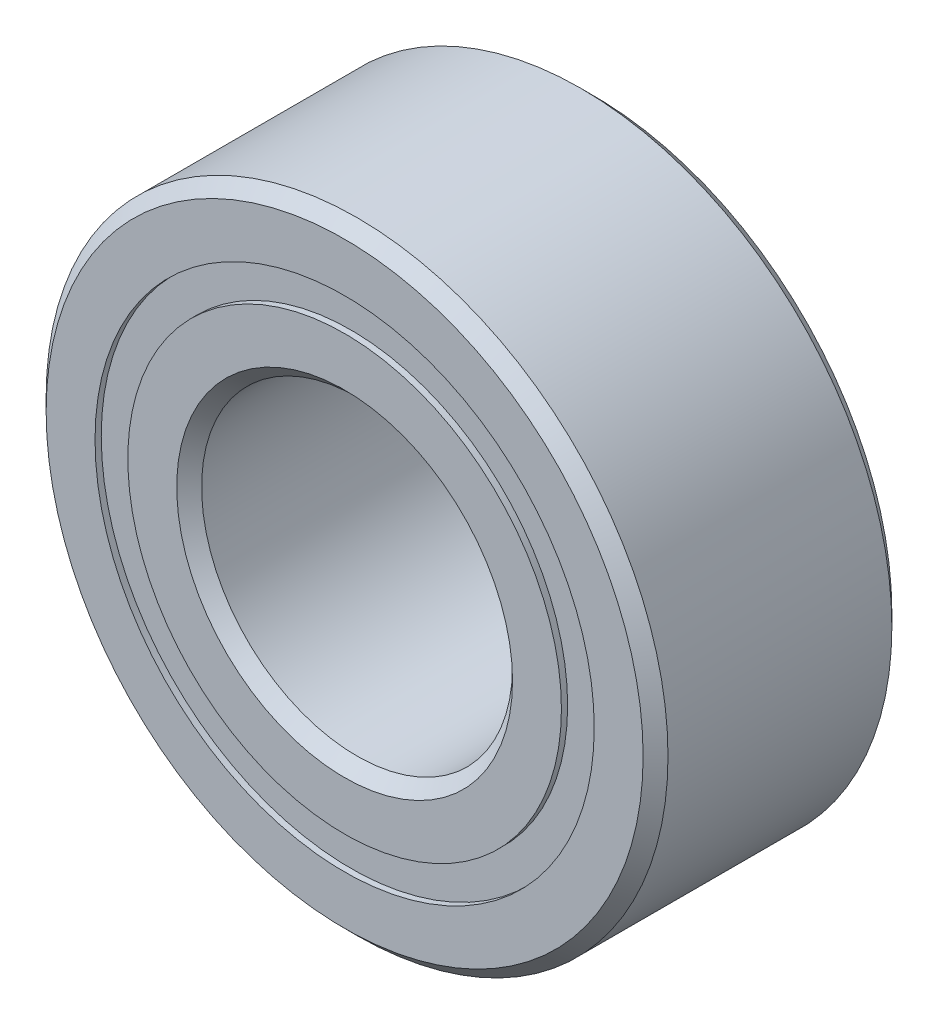
SolidWorks part; units mm, degrees
material "AISI 304"
ref_plane "Front Plane" through (0, 0, 0) normal (0, 0, 1) x (1, 0, 0)
ref_plane "Top Plane" through (0, 0, 0) normal (0, 1, 0) x (1, 0, 0)
ref_plane "Right Plane" through (0, 0, 0) normal (1, 0, 0) x (0, 0, -1)
sketch "Sketch1" plane through (0, 0, 0) normal (1, 0, 0) x (0, 0, -1)
  line L0 (-2, 0) -> (2, 0) construction
  line L1 (0, 5) -> (0, -5) construction
  line L2 (1.8, 5) -> (-1.8, 5)
  line L3 (-1.8, 5) -> (-2, 4.8)
  line L4 (-2, 4.8) -> (-2, 4.0137)
  line L5 (-2, 4.0137) -> (-0.8889, 4.0137)
  line L6 (2, 4.0137) -> (0.8889, 4.0137)
  line L7 (2, 4.8) -> (2, 4.0137)
  line L8 (1.8, 5) -> (2, 4.8)
  line L9 (0, 5) -> (0, 3.75) construction
  line L10 (0, 3.75) -> (0, 2.5) construction
  arc A0 (-0.8889, 4.0137) -> (0.8889, 4.0137) centre (0, 3.75) cw
  point P14 (0, 2.5)
  dimension "Width" = 4
  dimension "OD" = 10
  dimension "D1" = 45
  dimension "D2" = 0.2
  dimension "Shaft Dia" = 5
  dimension "D3" = 1.7778
  dimension "D4" = 0.2637
revolve "Revolve1" add sketch "Sketch1" angle 360 about L0
sketch "Sketch3" plane through (0, 0, 0) normal (1, 0, 0) x (0, 0, -1)
  line L0 (-2, 3.4863) -> (-0.8889, 3.4863)
  line L1 (0, 5) -> (0, -5) construction
  line L2 (-2, 4.8) -> (-2, 4.0137) construction
  line L3 (-2, 3.4863) -> (-2, 2.7)
  line L4 (-1.8, 5) -> (-2, 4.8) construction
  line L5 (-2, 2.7) -> (-1.8, 2.5)
  line L6 (-1.8, 2.5) -> (1.8, 2.5)
  line L7 (1.8, 5) -> (1.8, -5) construction
  line L8 (1.8, 2.5) -> (2, 2.7)
  line L9 (2, -4.8) -> (2, 4.8) construction
  line L10 (2, 2.7) -> (2, 3.4863)
  line L11 (2, 3.4863) -> (0.8889, 3.4863)
  line L13 (1.8, 5) -> (2, 4.8) construction
  arc A0 (0.8889, 4.0137) -> (-0.8889, 4.0137) centre (0, 3.75) ccw construction
  arc A1 (0.8889, 3.4863) -> (-0.8889, 3.4863) centre (0, 3.75) cw
revolve "Revolve3" add sketch "Sketch3" angle 360 about L0
sketch "Sketch4" plane through (0, 0, 0) normal (1, 0, 0) x (0, 0, -1)
  line L0 (-0.9272, 3.75) -> (0.9272, 3.75)
  arc A2 (-0.9272, 3.75) -> (0.9272, 3.75) centre (0, 3.75) cw
  arc A3 (0.8889, 4.0137) -> (-0.8889, 4.0137) centre (0, 3.75) ccw construction
revolve "Revolve4" add sketch "Sketch4" angle 360 about L0
ref_axis "Axis1" through (0, 0, -2) along (0, 0, 1)
pattern_circular "CirPattern1" count 12 every 30 about axis through (0, 0, -2) along (0, 0, 1) of bodies 104
sketch "Sketch5" plane through (0, 0, 0) normal (1, 0, 0) x (0, 0, -1)
  line L0 (-2, 4.0137) -> (-0.8889, 4.0137) construction
  line L1 (-1.9, 4.0137) -> (-0.9272, 4.0137)
  line L2 (-1.9, 4.0137) -> (-1.9, 3.4863)
  line L3 (-1.9, 3.4863) -> (-0.9272, 3.4863)
  line L4 (-0.9272, 4.0137) -> (-0.9272, 3.4863)
  line L5 (-2, 3.4863) -> (-0.8889, 3.4863) construction
  line L6 (2, 4.0137) -> (0.8889, 4.0137) construction
  line L7 (1.9, 4.0137) -> (0.9272, 4.0137)
  line L8 (1.9, 4.0137) -> (1.9, 3.4863)
  line L9 (1.9, 3.4863) -> (0.9272, 3.4863)
  line L10 (0.9272, 4.0137) -> (0.9272, 3.4863)
  line L11 (2, 3.4863) -> (0.8889, 3.4863) construction
  line L12 (-1.8, 5) -> (-2, 4.8) construction
  point P18 (-1.9, 4.9)
revolve "Revolve5" add sketch "Sketch5" angle 360 about L0
sketch "Sketch6" plane through (0, 0, 0) normal (1, 0, 0) x (0, 0, -1)
  line L0 (2, 0) -> (-2, 0) construction
  line L1 (2, 4.0137) -> (0.9, 4.0137)
  line L2 (2, 4.0137) -> (2, 9.5)
  line L3 (2, 9.5) -> (0.9, 9.5)
  line L4 (0.9, 4.0137) -> (0.9, 9.5)
  dimension "Th" = 1.1
  dimension "Flange OD" = 19
revolve "Revolve6" [suppressed] add sketch "Sketch6" angle 360 about L0
equation "\"D2@Sketch1\" = \"Width@Sketch1\"*.05"
equation "\"D3@Sketch1\" = \"Width@Sketch1\"/2.25"
equation "\"D4@Sketch1\" = (((\"OD@Sketch1\"-\"Width@Sketch1\")/2)/3.25)/3.5"
equation "\"D2@CirPattern1\" = 360/\"Balls@CirPattern1\""
